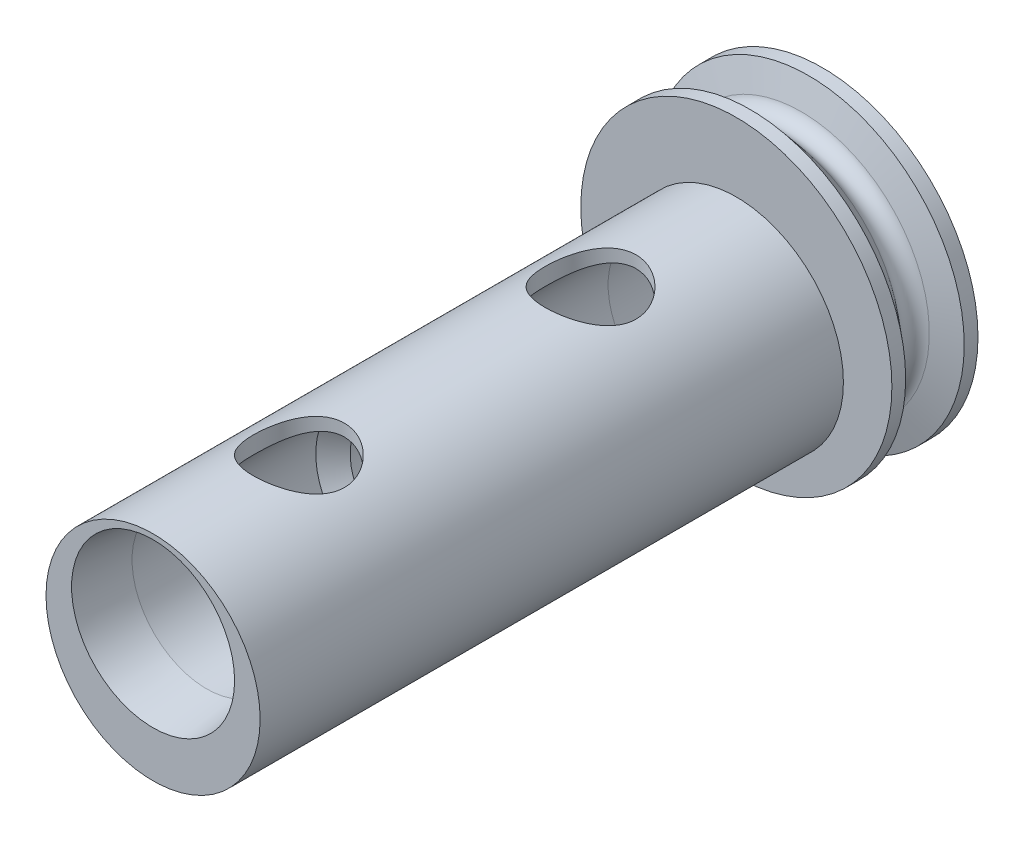
SolidWorks part; units mm, degrees
material "ABS"
ref_plane "Front Plane" through (0, 0, 0) normal (0, 0, 1) x (1, 0, 0)
ref_plane "Top Plane" through (0, 0, 0) normal (0, 1, 0) x (1, 0, 0)
ref_plane "Right Plane" through (0, 0, 0) normal (1, 0, 0) x (0, 0, -1)
sketch "Sketch1" plane through (0, 0, 0) normal (0, 0, 1) x (1, 0, 0)
  circle A1 centre (0, 0) radius 9.525 construction
  circle A2 centre (0, 0) radius 9.525 construction
  circle A3 centre (0, 0) radius 9.325
  dimension "D3" = 0.2
extrude "Boss-Extrude1" add sketch "Sketch1" against normal up to surface (50.8 mm away)
sketch "Sketch2" plane through (0, 0, 0) normal (0, 1, 0) x (1, 0, 0)
  circle A0 centre (0, 38.1) radius 3.9688
  circle A1 centre (0, 12.7) radius 3.9688
  dimension "D1" = 7.9375
extrude "Cut-Extrude1" cut sketch "Sketch2" along normal blind 10.16 from offset 1.27
ref_axis "Axis1" through (0, 1.778, -24.4249) along (0, 0, 1)
sketch "Sketch3" plane through (0, 0, 0) normal (1, 0, 0) x (0, 0, -1)
  line L0 (50.8, 1.778) -> (50.8, 15.325)
  line L1 (50.8, 15.325) -> (52, 15.325)
  line L2 (52, 15.325) -> (54.3954, 12.4702)
  line L3 (56.4576, 12.9274) -> (57.1, 15.325)
  line L4 (57.1, 15.325) -> (58.3, 15.325)
  line L5 (58.3, 15.325) -> (58.3, 1.778)
  line L6 (58.3, 1.778) -> (50.8, 1.778)
  line L7 (50.8, -9.325) -> (50.8, 9.325) construction
  line L8 (24.4249, 1.778) -> (-26.3751, 1.778) construction
  line L9 (50.8, 9.325) -> (42.0688, 9.325) construction
  arc A0 (54.3954, 12.4702) -> (56.4576, 12.9274) centre (55.3075, 13.2355) ccw
  point P16 (46.4344, 9.325)
  dimension "D1" = 50
  dimension "D3" = 1.1906
  dimension "D2" = 1.2
  dimension "D4" = 6
  dimension "D5" = 75
  dimension "D6" = 7.5
revolve "Revolve1" add sketch "Sketch3" angle 360 about axis through (0, 1.778, -24.4249) along (0, 0, 1)
sketch "Sketch4" plane through (0, 0, 0) normal (0, 0, 1) x (1, 0, 0)
  point P0 (0, 1.775)
  point P1 (0, 0)
  dimension "D1" = 1.775
sketch "Sketch5" plane through (0, 0, 0) normal (1, 0, 0) x (0, 0, -1)
  line L0 (0, 1.778) -> (58.3, 1.778)
  line L3 (24.4249, 1.778) -> (-26.3751, 1.778) construction
  line L4 (0, 9.325) -> (0, -9.325) construction
  line L5 (58.3, -11.769) -> (58.3, 15.325) construction
  line L6 (4.6687, 8.278) -> (20.6687, 8.278)
  line L7 (30.1313, 8.278) -> (46.1313, 8.278)
  line L8 (20.6687, 8.278) -> (22.1687, 6.778)
  line L9 (22.1687, 6.778) -> (28.6313, 6.778)
  line L10 (28.6313, 6.778) -> (30.1313, 8.278)
  line L11 (34.1313, 9.325) -> (16.6687, 9.325) construction
  line L12 (4.6687, 8.278) -> (0, 8.878)
  line L13 (46.1313, 8.278) -> (58.3, 8.878)
  line L14 (0, 8.878) -> (0, 1.778)
  line L15 (58.3, 8.878) -> (58.3, 1.778)
  spline S0 degree 2 poles (16.6687, 9.325) (12.7, 7.6359) (8.7312, 9.325) knots 0 0 0 1 1 1 weights 0.005356 0.009325 0.013294 construction
  point P13 (25.4, 9.325)
  point P16 (25.4, 6.778)
  point P25 (16.6687, 9.325)
  dimension "D1" = 16
  dimension "D2" = 45
  dimension "D3" = 6.5
  dimension "D4" = 0.6
  dimension "D5" = 4
  dimension "D6" = 5
revolve "Cut-Revolve1" cut sketch "Sketch5" angle 360 about L0
